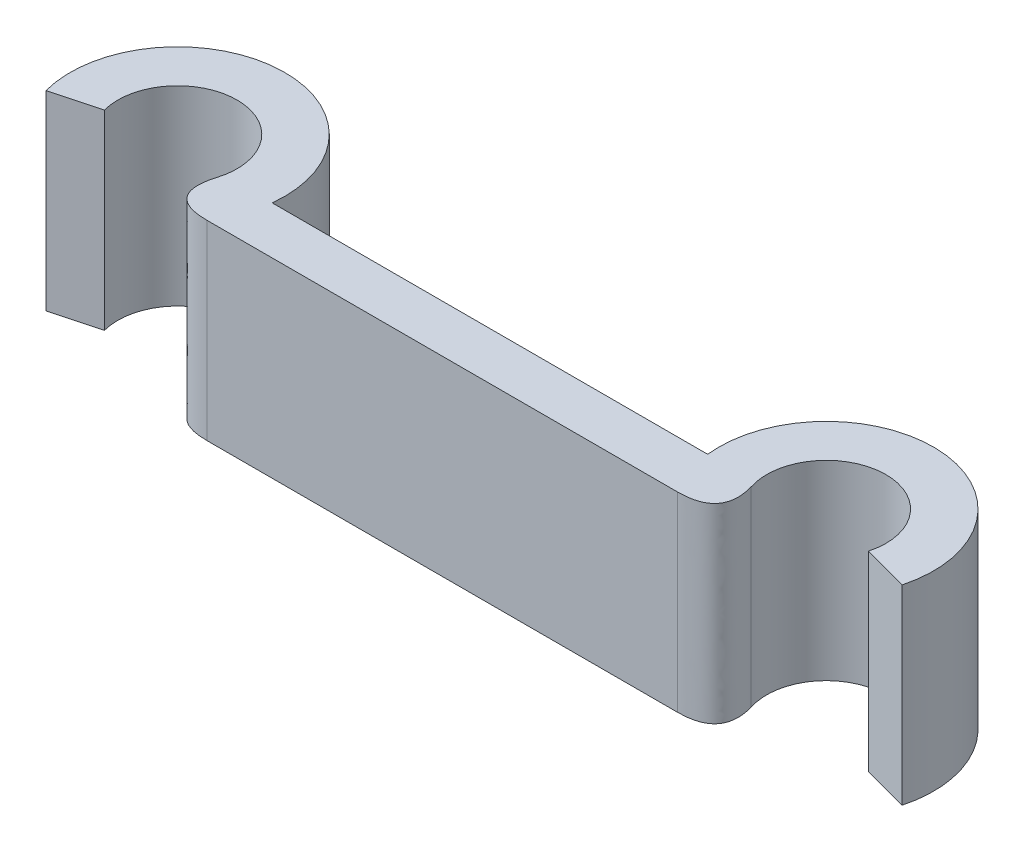
SolidWorks part; units mm, degrees
ref_plane "Front Plane" through (0, 0, 0) normal (0, 0, 1) x (1, 0, 0)
ref_plane "Top Plane" through (0, 0, 0) normal (0, 1, 0) x (1, 0, 0)
ref_plane "Right Plane" through (0, 0, 0) normal (1, 0, 0) x (0, 0, -1)
sketch "Sketch1" plane through (0, 0, 0) normal (0, 1, 0) x (1, 0, 0)
  line L0 (-22.5386, 0) -> (20.6101, 0) construction
  line L1 (0, 0) -> (0, 25.8531) construction
  line L2 (-17, 0) -> (-22.4333, -1.4559)
  line L3 (-17, 0) -> (-17, 5.625) construction
  line L4 (-17, 0) -> (-11.5667, -1.4559)
  line L5 (-17, -3.125) -> (0, -3.125) construction
  line L6 (0, -0.625) -> (-11.4098, -0.625)
  line L7 (0, -3.125) -> (-12.3229, -3.125)
  line L8 (0, -3.125) -> (0, -0.625)
  circle A0 centre (-17, 0) radius 3.125
  circle A1 centre (-17, 0) radius 5.625
  spline S0 degree 2 poles (-12.3229, -3.125) (-14.7143, -3.1309) (-13.9815, -0.8088) knots 0 0 0 1 1 1
  dimension "D1" = 6.25
  dimension "D2" = 34
  dimension "D4" = 15
  dimension "D5" = 2.5
  dimension "D3" = 2.5
extrude "Boss-Extrude1" add sketch "Sketch1" along normal blind 10 contours A1 L7 L8 L6 | S0 A1 L4 A0 | L4 A1 L2 A0 region at (-21.2603, 0, 1.0039) region at (-12.9784, 0, 1.9852) region at (-5.8793, 0, 1.891)
mirror "Mirror1" about plane through (0, 0, 0) normal (1, 0, 0) of "Boss-Extrude1"
